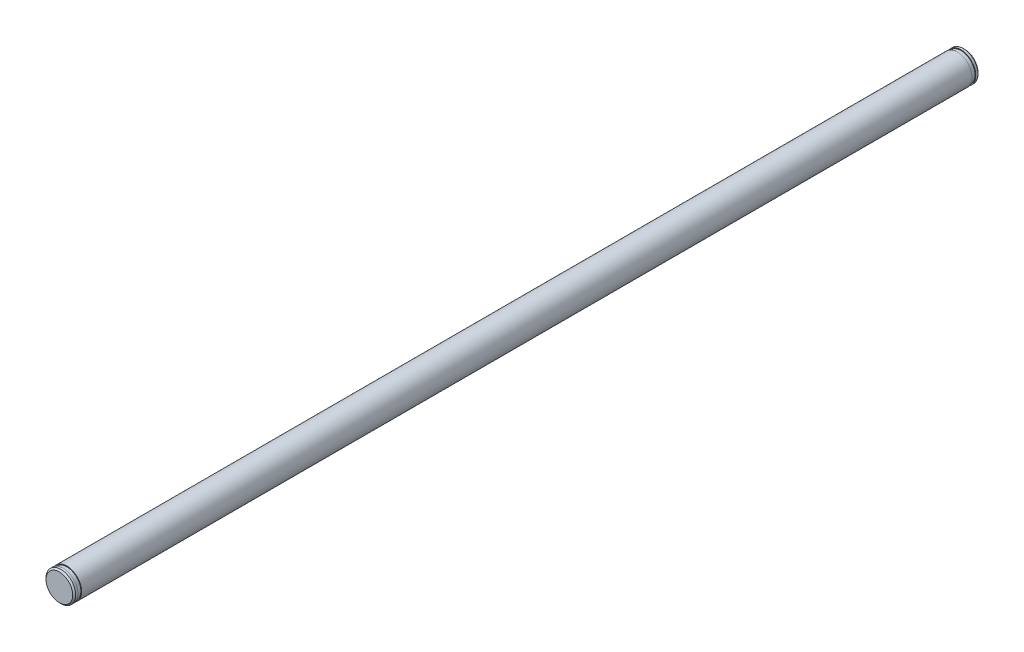
SolidWorks part; units mm, degrees
ref_plane "Vorne" through (0, 0, 0) normal (0, 0, 1) x (1, 0, 0)
ref_plane "Oben" through (0, 0, 0) normal (0, 1, 0) x (1, 0, 0)
ref_plane "Seite" through (0, 0, 0) normal (1, 0, 0) x (0, 0, -1)
sketch "Skizze1" plane through (0, 0, 0) normal (0, 0, 1) x (1, 0, 0)
  circle A0 centre (0, 0) radius 2
  point P3 (0, -3)
  dimension "D1" = 4
  dimension "D2" = 3
extrude "Aufsatz-Linear austragen1" add sketch "Skizze1" along normal mid plane 122
sketch "Skizze2" plane through (0, 0, 61) normal (0, 0, 1) x (1, 0, 0)
  point P0 (0, 0)
sketch "Skizze7" plane through (0, 0, 0) normal (1, 0, 0) x (0, 0, -1)
  line L0 (-60.5, 2) -> (-60.5, 1.9)
  line L1 (61, 2) -> (-61, 2) construction
  line L2 (-60.5, 1.9) -> (-60, 1.9)
  line L3 (-60, 1.9) -> (-60, 2)
  line L4 (-60, 2) -> (-60.5, 2)
  line L5 (60, 2) -> (60, 1.9)
  line L6 (60, 1.9) -> (60.5, 1.9)
  line L7 (60.5, 1.9) -> (60.5, 2)
  line L8 (60.5, 2) -> (60, 2)
  line L9 (-61, 2) -> (-61, -2) construction
  line L10 (61, 0) -> (-61, 0) construction
  line L11 (61, -2) -> (61, 2) construction
  dimension "D1" = 0.1
  dimension "D2" = 0.5
  dimension "D3" = 0.5
  dimension "D4" = 120
revolve "Schnitt-Rotation1" cut sketch "Skizze7" angle 360 about L10
chamfer "Fase1" distance 0.2 angle 45 2 edges at (2, 0, -61) (2, 0, 61)
